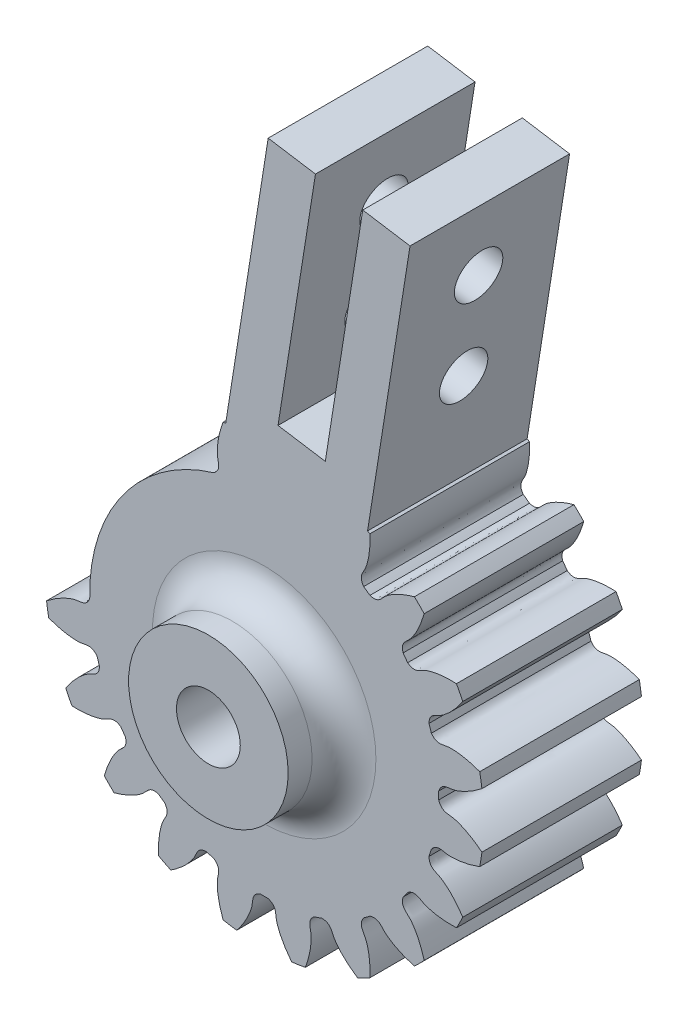
SolidWorks part; units mm, degrees
note: '?' marks a value the reader was unsure of.
material "聚脂树脂"
ref_plane "前视基准面" through (0, 0, 0) normal (0, 0, 1) x (1, 0, 0)
ref_plane "上视基准面" through (0, 0, 0) normal (0, 1, 0) x (1, 0, 0)
ref_plane "右视基准面" through (0, 0, 0) normal (1, 0, 0) x (0, 0, -1)
other "Configuration Table"
sketch "草图1" plane through (0, 0, 0) normal (0, 0, 1) x (1, 0, 0)
  circle A0 centre (0, 0) radius 13.75
extrude "凸台-拉伸1" add sketch "草图1" along normal blind 10
ref_axis "基准轴1" through (0, 0, -1.5) along (0, 0, 1)?
sketch "草图2" plane through (0, 0, 0) normal (0, 0, 1) x (1, 0, 0)
  line L0 (0, 0) -> (0, 13.75) construction
  circle A0 centre (0, 0) radius 13.75 construction
  arc A1 (0.2416, 10.9348) -> (-0.2416, 10.9348) centre (0, 0) ccw
  arc A2 (3.9764, 15.6228) -> (-3.9764, 15.6228) centre (0, 0) ccw
  spline S0 degree 3 poles (0.2416, 10.9348) (0.764, 11.1168) (0.6964, 11.4839) (0.7661, 11.8375) (0.7736, 11.8719) (0.7829, 11.9108) (0.7941, 11.954) (0.8075, 12.0015) (0.8231, 12.0532) (0.8413, 12.1091) (0.8621, 12.169) (0.8857, 12.2329) (0.9123, 12.3007) (0.9421, 12.3723) (0.9752, 12.4476) (1.0117, 12.5264) (1.0519, 12.6088) (1.0959, 12.6945) (1.1438, 12.7834) (1.1957, 12.8755) (1.2519, 12.9705) (1.3125, 13.0684) (1.3775, 13.1691) (1.4472, 13.2723) (1.5216, 13.3779) (1.601, 13.4858) (1.6853, 13.5958) (1.7747, 13.7078) (1.8694, 13.8216) (1.9693, 13.937) (2.0748, 14.0539) (2.1857, 14.1721) (2.3023, 14.2914) (2.4246, 14.4116) (2.5527, 14.5326) (2.6866, 14.6542) (2.8265, 14.7761) (2.9725, 14.8983) (3.1245, 15.0204) (3.2826, 15.1424) (3.4469, 15.2639) (3.6768, 15.427) (3.8549, 15.5454) (3.9764, 15.6228) knots 0 0 0 0 0.165916 0.170906 0.176664 0.183189 0.190482 0.198542 0.207371 0.216967 0.22733 0.238462 0.250361 0.263027 0.276462 0.290664 0.305634 0.321371 0.337876 0.355149 0.37319 0.391998 0.411574 0.431917 0.453028 0.474907 0.497554 0.520968 0.54515 0.570099 0.595817 0.622302 0.649554 0.677575 0.706363 0.735918 0.766242 0.797333 0.829191 0.861818 0.895212 0.929373 1 1 1 1
  spline S1 degree 3 poles (-0.2416, 10.9348) (-0.764, 11.1168) (-0.6964, 11.4839) (-0.7661, 11.8375) (-0.7736, 11.8719) (-0.7829, 11.9108) (-0.7941, 11.954) (-0.8075, 12.0015) (-0.8231, 12.0532) (-0.8413, 12.1091) (-0.8621, 12.169) (-0.8857, 12.2329) (-0.9123, 12.3007) (-0.9421, 12.3723) (-0.9752, 12.4476) (-1.0117, 12.5264) (-1.0519, 12.6088) (-1.0959, 12.6945) (-1.1438, 12.7834) (-1.1957, 12.8755) (-1.2519, 12.9705) (-1.3125, 13.0684) (-1.3775, 13.1691) (-1.4472, 13.2723) (-1.5216, 13.3779) (-1.601, 13.4858) (-1.6853, 13.5958) (-1.7747, 13.7078) (-1.8694, 13.8216) (-1.9693, 13.937) (-2.0748, 14.0539) (-2.1857, 14.1721) (-2.3023, 14.2914) (-2.4246, 14.4116) (-2.5527, 14.5326) (-2.6866, 14.6542) (-2.8265, 14.7761) (-2.9725, 14.8983) (-3.1245, 15.0204) (-3.2826, 15.1424) (-3.4469, 15.2639) (-3.6768, 15.427) (-3.8549, 15.5454) (-3.9764, 15.6228) knots 0 0 0 0 0.165916 0.170906 0.176664 0.183189 0.190482 0.198542 0.207371 0.216967 0.22733 0.238462 0.250361 0.263027 0.276462 0.290664 0.305634 0.321371 0.337876 0.355149 0.37319 0.391998 0.411574 0.431917 0.453028 0.474907 0.497554 0.520968 0.54515 0.570099 0.595817 0.622302 0.649554 0.677575 0.706363 0.735918 0.766242 0.797333 0.829191 0.861818 0.895212 0.929373 1 1 1 1
extrude "切除-拉伸1" cut sketch "草图2" along normal through all
pattern_circular "阵列(圆周)1" count 20 every 18 about axis through (0, 0, -1.5) along (0, 0, 1) of "切除-拉伸1"
sketch "草图3" plane through (0, 0, 0) normal (0, 0, 1) x (1, 0, 0)
  circle A0 centre (0, 0) radius 12.5 construction
  dimension "Dn" = 25
sketch "草图6" plane through (0, 0, 0) normal (0, 0, -1) x (-1, 0, 0)
  line L0 (0, 0) -> (-10.311, 65.1009) construction
  line L1 (0, 0) -> (38.9643, 6.1713) construction
  line L2 (0, 0) -> (-30.4582, -4.8241) construction
  line L3 (-12.3461, -1.9554) -> (-21.1812, 53.827) construction
  line L4 (4.4446, 0.704) -> (-1.1233, 35.8583)
  line L5 (-4.4446, -0.704) -> (-10.0125, 34.4504)
  line L6 (-10.0125, 34.4504) -> (-15.7198, 70.4851)
  line L7 (-15.7198, 70.4851) -> (-21.4537, 55.5478) construction
  line L8 (-15.7198, 70.4851) -> (-7.9754, 90.6601) construction
  line L9 (-15.7198, 70.4851) -> (-11.3112, 81.9699)
  line L10 (-4.4446, -0.704) -> (4.4446, 0.704)
  circle A0 centre (0, 0) radius 12.5 construction
  circle A1 centre (-21.4537, 55.5478) radius 24 construction
  circle A2 centre (-21.4537, 55.5478) radius 28.3019 construction
  arc A3 (-11.3112, 81.9699) -> (-1.1233, 35.8583) centre (-21.4537, 55.5478) cw
  dimension "D1" = 25
  dimension "D4" = 48
  dimension "D5" = 30
  dimension "D2" = 9
  dimension "D3" = 58.22
extrude "凸台-拉伸2" add sketch "草图6" against normal blind 15 and the other way blind 5
sketch "草图7" plane through (4.4446, -0.704, 0) normal (0.9877, -0.1564, 0) x (0, 0, -1)
  line L0 (0, 0) -> (0, 32)
  line L1 (0, 32) -> (5, 32)
  line L2 (5, 0) -> (5, 72.0764) construction
  line L3 (5, 32) -> (5, 0)
  line L4 (5, 0) -> (0, 0) construction
  line L5 (5, 0) -> (5, 72.0764) construction
  line L6 (5, 0) -> (0, 0)
  line L7 (-5, 4.6588) -> (-5, 27.3083) construction
  line L8 (-10, 4.6588) -> (0, 4.6588) construction
  line L9 (-15, 32) -> (-15, 0)
  line L10 (-10, 32) -> (-15, 32)
  line L11 (-10, 0) -> (-10, 32)
  line L12 (-15, 0) -> (-10, 0)
  dimension "D1" = 32
extrude "切除-拉伸3" cut sketch "草图7" against normal blind 32 and the other way blind 10
ref_plane "基准面1" through (12.5, 0, 0) normal (1, 0, 0) x (0, 0, -1)
ref_axis "基准轴2" through (0, 0, -6) along (0, 0, 1)?
ref_plane "基准面2" through (0, 0, 0) normal (-0.9877, 0.1564, 0) x (0, 0, 1)
ref_plane "基准面3" through (12.3461, -1.9554, 0) normal (-0.9877, 0.1564, 0) x (0, 0, 1)
sketch "草图13" plane through (12.3461, -1.9554, 0) normal (-0.9877, 0.1564, 0) x (0, 0, 1)
  line L0 (5, 0.4331) -> (5, 90.5431) construction
  line L1 (0, 0.4331) -> (10, 0.4331) construction
  line L2 (5, 82.6531) -> (5, 34.6531)
  arc A0 (5, 82.6531) -> (5, 34.6531) centre (5, 58.6531) cw
  dimension "D1" = 24
  dimension "D2" = 58.22
revolve "切除-旋转2" cut sketch "草图13" angle 360 about L0
sketch "草图12" plane through (0, 0, -5) normal (0, 0, -1) x (-1, 0, 0)
  line L0 (0, 0) -> (-14.3434, 90.5607) construction
  line L1 (-12.3461, -1.9554) -> (-26.4984, 87.3984) construction
  line L2 (-11.6703, 81.0345) -> (-11.3112, 81.9699)
  line L3 (0, 0) -> (-28.4747, -4.5099) construction
  line L4 (-1.1233, 35.8583) -> (-1.3214, 37.1092)
  line L5 (-0.5613, 32.31) -> (-1.1233, 35.8583) construction
  line L6 (-13.501, 76.2653) -> (-11.3112, 81.9699) construction
  circle A0 centre (-21.4537, 55.5478) radius 28.3019
  circle A1 centre (-21.4537, 55.5478) radius 27.3
  dimension "D3" = 54.6
  dimension "D4" = 56.6039
  dimension "D1" = 12.5
  dimension "D2" = 58.22
extrude "切除-拉伸4" cut sketch "草图12" against normal blind 22
fillet "圆角2" radius 2 4 edges at (5.0059, 31.606, 10) (5.0059, 31.606, 15) (5.0059, 31.606, 0) (5.0059, 31.606, -5)
fillet "圆角3" radius 3 2 edges at (-5.1188, 61.8083, 15) (-5.1188, 61.8083, -5)
sketch "草图16" plane through (0, 0, 10) normal (0, 0, 1) x (1, 0, 0)
  circle A0 centre (0, 0) radius 2
  dimension "D1" = 4
extrude "切除-拉伸5" cut sketch "草图16" against normal blind 16.5
sketch "草图18" plane through (0, 0, 10) normal (0, 0, 1) x (1, 0, 0)
  circle A0 centre (0, 0) radius 5
  circle A1 centre (0, 0) radius 2
  dimension "D1" = 10
  dimension "D2" = 4
extrude "凸台-拉伸4" add sketch "草图18" along normal blind 3.5
sketch "草图19" plane through (0, 0, 0) normal (0, 0, -1) x (-1, 0, 0)
  circle A0 centre (0, 0) radius 8
  dimension "D1" = 16
extrude "切除-拉伸7" cut sketch "草图19" against normal blind 3
fillet "圆角4" radius 2 1 edges at (5, 0, 10)
sketch "草图20" plane through (0, 0, 0) normal (0, 0, -1) x (-1, 0, 0)
  line L0 (0, 0) -> (3.6089, 10.325)
  line L1 (3.6089, 10.325) -> (7.1451, 20.4421)
  line L2 (0, 0) -> (10.9348, -0.2416)
  line L3 (10.9348, -0.2416) -> (20.7519, -0.2416)
  circle A0 centre (0, 0) radius 17.5
  circle A1 centre (0, 0) radius 10.9375
  arc A2 (-8.7044, 6.6228) -> (-8.9885, 6.2318) centre (0, 0) ccw construction
  dimension "D1" = 35
extrude "切除-拉伸8" cut sketch "草图20" against normal blind 10 contours A1 L3 A0 L1
sketch "草图21" plane through (0, 0, 0) normal (0, 0, -1) x (-1, 0, 0)
  line L0 (0, 0) -> (0, 79.6927) construction
  line L1 (0, 0) -> (-12.0171, 75.8728) construction
  line L2 (0, 0) -> (62.9966, 9.9777) construction
  line L3 (-3.828, 14.5807) -> (-0.865, 15.05)
  line L4 (-0.865, 15.05) -> (-3.2115, 29.8653)
  line L5 (-3.2115, 29.8653) -> (16.5423, 32.994)
  line L6 (16.5423, 32.994) -> (7.3328, 91.1406)
  line L7 (7.3328, 91.1406) -> (-13.9232, 87.774)
  line L8 (0, 0) -> (-24.6264, 75.7922) construction
  line L9 (-35.1378, 84.4139) -> (-13.9232, 87.774)
  line L10 (-25.9283, 26.2673) -> (-35.1378, 84.4139)
  line L11 (-6.1746, 29.396) -> (-25.9283, 26.2673)
  line L12 (-3.828, 14.5807) -> (-6.1746, 29.396)
  point P17 (-2.3465, 14.8153)
  dimension "D1" = 9
  dimension "D2" = 15
  dimension "D3" = 1.5
  dimension "D4" = 15
  dimension "D5" = 20
  dimension "D6" = 58.8714
extrude "切除-拉伸9" cut sketch "草图21" against normal blind 22 and the other way blind 36
sketch "草图22" plane through (4.4446, -0.704, 0) normal (0.9877, -0.1564, 0) x (0, 0, -1)
  line L0 (-5, -13.7432) -> (-5, 31.5742) construction
  line L1 (-10, -13.7432) -> (0, -13.7432) construction
  line L2 (0, 30) -> (-10, 30) construction
  circle A0 centre (-5, 25.5) radius 1.5
  circle A1 centre (-5, 19.5) radius 1.5
  dimension "D1" = 3
  dimension "D2" = 3
  dimension "D3" = 6
  dimension "D4" = 4.5
extrude "切除-拉伸10" cut sketch "草图22" against normal blind 10
